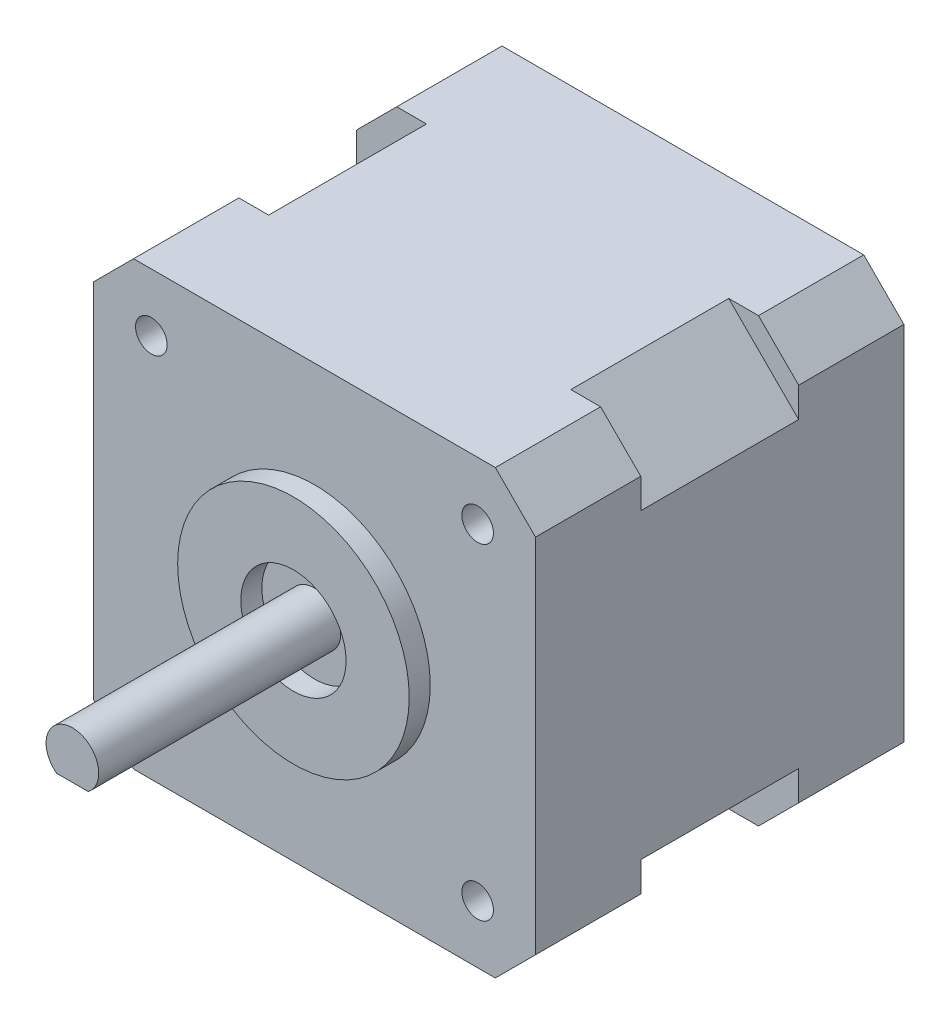
SolidWorks part; units mm, degrees
ref_plane "前视基准面" through (0, 0, 0) normal (0, 0, 1) x (1, 0, 0)
ref_plane "上视基准面" through (0, 0, 0) normal (0, 1, 0) x (1, 0, 0)
ref_plane "右视基准面" through (0, 0, 0) normal (1, 0, 0) x (0, 0, -1)
sketch "草图1" plane through (0, 0, 0) normal (0, 0, 1) x (1, 0, 0)
  line L5 (-17.1838, 21) -> (17.1838, 21)
  line L7 (-21, 17.1838) -> (-17.1838, 21)
  line L9 (21, 17.1838) -> (17.1838, 21)
  line L10 (-17.1838, -21) -> (-21, -17.1838)
  line L11 (-21, 17.1838) -> (-21, -17.1838)
  line L12 (17.1838, -21) -> (-17.1838, -21)
  line L13 (17.1838, -21) -> (21, -17.1838)
  line L14 (21, -17.1838) -> (21, 17.1838)
  point P0 (0, 0)
extrude "凸台-拉伸1" add sketch "草图1" along normal blind 35
sketch "草图2" plane through (0, 0, 35) normal (0, 0, 1) x (1, 0, 0)
  circle A0 centre (0, 0) radius 11
  circle A1 centre (0, 0) radius 5
extrude "凸台-拉伸2" add sketch "草图2" along normal blind 2
sketch "草图3" plane through (0, 0, 35) normal (0, 0, 1) x (1, 0, 0)
  circle A0 centre (0, 0) radius 2.5
extrude "凸台-拉伸3" add sketch "草图3" along normal blind 23
sketch "草图4" plane through (0, 0, 58) normal (0, 0, 1) x (1, 0, 0)
  line L2 (1.5, -2) -> (-1.5, -2)
  circle A1 centre (0, 0) radius 2.5
  arc A2 (-1.5, -2) -> (1.5, -2) centre (0, 0) ccw
  dimension "D1" = 0
extrude "切除-拉伸1" cut sketch "草图4" against normal blind 18
sketch "草图5" plane through (0, 0, 35) normal (0, 0, 1) x (1, 0, 0)
  circle A0 centre (-15.5, 15.5) radius 1.5
  circle A1 centre (15.5, 15.5) radius 1.5
  circle A2 centre (15.5, -15.5) radius 1.5
  circle A3 centre (-15.5, -15.5) radius 1.5
  point P0 (0, 0)
  point P7 (0, 0)
  point P10 (0, 0)
  point P13 (0, 0)
  point P16 (0, 0)
  dimension "D1" = 4
extrude "切除-拉伸2" cut sketch "草图5" against normal blind 5
sketch "草图6" plane through (0, 0, 0) normal (0, 0, -1) x (-1, 0, 0)
  circle A0 centre (0, 0) radius 4.5
extrude "切除-拉伸3" cut sketch "草图6" against normal blind 3
ref_plane "基准面1" through (0, 0, 10) normal (0, 0, -1) x (-1, 0, 0)
sketch "草图7" plane through (0, 0, 10) normal (0, 0, -1) x (-1, 0, 0)
  line L1 (14.3553, 21) -> (21, 14.3553)
  line L5 (21, -14.3553) -> (21, 14.3553)
  line L6 (14.3553, -21) -> (21, -14.3553)
  line L9 (14.3553, -21) -> (-14.3553, -21)
  line L10 (-21, -14.3553) -> (-14.3553, -21)
  line L11 (-21, 14.3553) -> (-21, -14.3553)
  line L12 (-21, 14.3553) -> (-14.3553, 21)
  line L13 (-14.3553, 21) -> (14.3553, 21)
  line L15 (-38.595, -30.982) -> (38.595, -30.982)
  line L16 (-38.595, -30.982) -> (-38.595, 30.982)
  line L17 (-38.595, 30.982) -> (38.595, 30.982)
  line L18 (38.595, -30.982) -> (38.595, 30.982)
  line L19 (-38.595, -30.982) -> (38.595, 30.982) construction
  line L20 (-38.595, 30.982) -> (38.595, -30.982) construction
  point P1 (0, 0)
extrude "切除-拉伸4" cut sketch "草图7" against normal blind 15
